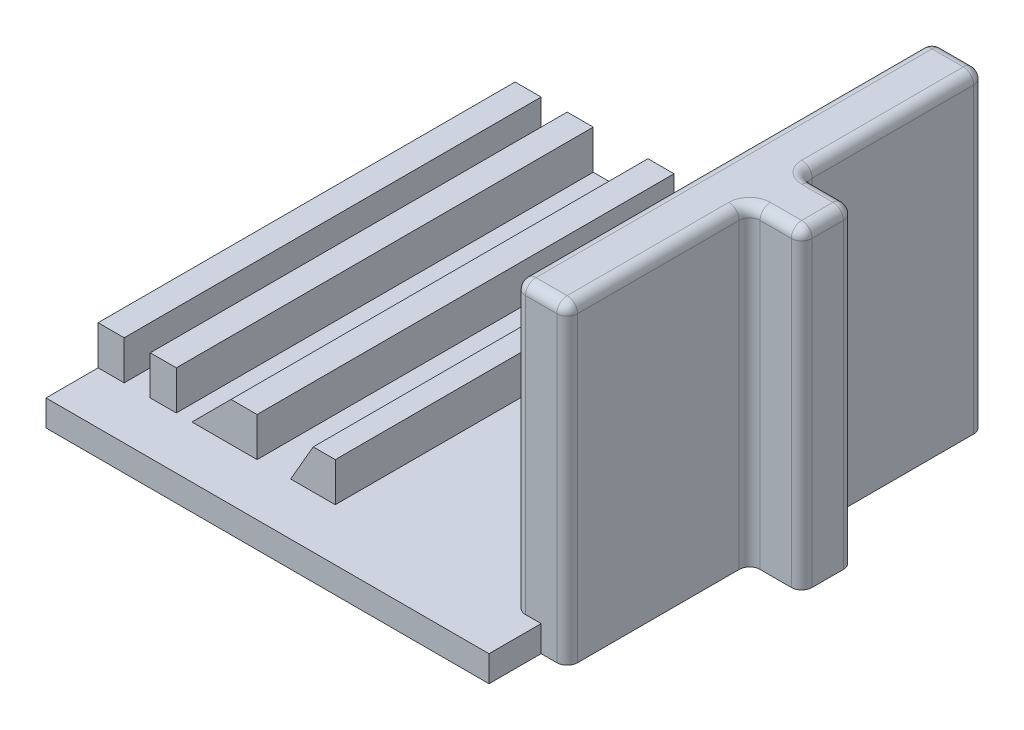
SolidWorks part; units mm, degrees
ref_plane "Front Plane" through (0, 0, 0) normal (0, 0, 1) x (1, 0, 0)
ref_plane "Top Plane" through (0, 0, 0) normal (0, 1, 0) x (1, 0, 0)
ref_plane "Right Plane" through (0, 0, 0) normal (1, 0, 0) x (0, 0, -1)
sketch "Sketch1" plane through (0, 0, 0) normal (0, 1, 0) x (1, 0, 0)
  line L0 (-25.4, 203.2) -> (-25.4, 0)
  line L1 (0, 0) -> (-25.4, 0)
  line L2 (0, 0) -> (0, 203.2)
  line L3 (0, 203.2) -> (-25.4, 203.2)
  line L4 (-25.4, 0) -> (-25.4, 203.2)
  line L5 (-25.4, 203.2) -> (-228.6, 203.2)
  line L6 (-25.4, 0) -> (-228.6, 0)
  line L7 (-228.6, 203.2) -> (-228.6, 0)
  line L8 (0, 101.6) -> (-228.6, 101.6) construction
  line L9 (0, 101.6) -> (104.3179, 101.6)
  line L10 (0, 114.3) -> (0, 88.9)
  line L13 (0, 114.3) -> (25.4, 114.3)
  line L14 (0, 88.9) -> (25.4, 88.9)
  line L15 (25.4, 114.3) -> (25.4, 88.9)
  dimension "D1" = 25.4
  dimension "D2" = 203.2
  dimension "D3" = 88.9
  dimension "D4" = 88.9
  dimension "D5" = 203.2
  dimension "D6" = 25.4
  dimension "D7" = 0
extrude "Boss-Extrude1" add sketch "Sketch1" along normal blind 12.7 contours L8 L0 L5 L7 | L4 L8 L7 L6 region at (-127, 0, -152.4) region at (-127, 0, -50.8)
sketch "Sketch2" plane through (0, 0, 0) normal (0, 1, 0) x (1, 0, 0)
  line L0 (-25.4, 0) -> (-25.4, 203.2)
  line L1 (-25.4, 0) -> (0, 0)
  line L2 (-25.4, 203.2) -> (0, 203.2)
  line L3 (0, 0) -> (0, 203.2)
  dimension "D1" = 25.4
sketch "Sketch3" plane through (0, 0, 0) normal (0, 1, 0) x (1, 0, 0)
  line L0 (0, 88.9) -> (0, 114.3)
  line L1 (0, 88.9) -> (25.4, 88.9)
  line L2 (0, 114.3) -> (25.4, 114.3)
  line L3 (25.4, 88.9) -> (25.4, 114.3)
  line L4 (0, 0) -> (0, 203.2) construction
  line L5 (-25.4, 203.2) -> (-228.6, 203.2) construction
  line L6 (-25.4, 0) -> (-228.6, 0) construction
  dimension "D1" = 88.9
  dimension "D2" = 88.9
  dimension "1" = 25.4
extrude "Boss-Extrude2" add sketch "Sketch2" along normal blind 152.4
extrude "Boss-Extrude3" add sketch "Sketch3" along normal blind 152.4
fillet "Fillet1" radius 5.08 16 edges at (-25.4, 152.4, -101.6) (-12.7, 152.4, -203.2) (0, 152.4, -158.75) (12.7, 152.4, -114.3) (25.4, 152.4, -101.6) (12.7, 152.4, -88.9) (0, 152.4, -44.45) (-12.7, 152.4, 0) (-25.4, 82.55, -203.2) (0, 76.2, -203.2) (0, 76.2, -114.3) (25.4, 76.2, -114.3) (25.4, 76.2, -88.9) (-25.4, 82.55, 0) (0, 76.2, 0) (0, 76.2, -88.9)
sketch "Sketch4" plane through (0, 12.7, 0) normal (0, 1, 0) x (1, 0, 0)
  line L0 (-203.2, 203.2) -> (-203.2, 0)
  line L1 (-203.2, 203.2) -> (-190.5, 203.2)
  line L2 (-203.2, 0) -> (-190.5, 0)
  line L3 (-190.5, 203.2) -> (-190.5, 0)
  line L4 (-20.32, 203.2) -> (-228.6, 203.2) construction
  line L5 (-20.32, 0) -> (-228.6, 0) construction
  line L6 (-228.6, 203.2) -> (-228.6, 0) construction
  line L7 (-189.23, 203.2) -> (-189.23, 0)
  line L8 (-189.23, 203.2) -> (-151.13, 203.2)
  line L9 (-189.23, 0) -> (-151.13, 0)
  line L10 (-151.13, 203.2) -> (-151.13, 0)
  line L11 (-138.43, 203.2) -> (-138.43, 0)
  line L12 (-138.43, 203.2) -> (-113.03, 203.2)
  line L13 (-138.43, 0) -> (-113.03, 0)
  line L14 (-113.03, 203.2) -> (-113.03, 0)
  line L15 (-228.6, 203.2) -> (-228.6, 0)
  line L16 (-228.6, 203.2) -> (-215.9, 203.2)
  line L17 (-228.6, 0) -> (-215.9, 0)
  line L18 (-215.9, 203.2) -> (-215.9, 0)
  dimension "D1" = 25.4
  dimension "D2" = 12.7
  dimension "D3" = 1.27
  dimension "D4" = 38.1
  dimension "D5" = 12.7
  dimension "D6" = 25.4
  dimension "D7" = 12.7
extrude "Boss-Extrude4" add sketch "Sketch4" along normal blind 19.05
chamfer "Chamfer1" distance 25.4 angle 45 1 edges at (-189.23, 31.75, -101.6)
chamfer "Chamfer2" distance 25.4 angle 30 1 edges at (-138.43, 31.75, -101.6) first distance on face at (-138.43, 22.225, -101.6)
sketch "Sketch6" plane through (0, 0, 0) normal (0, 1, 0) x (1, 0, 0)
  line L0 (-228.6, 0) -> (-12.7, 0)
  line L1 (-228.6, 0) -> (-228.6, -25.4)
  line L2 (-12.7, 0) -> (-12.7, -25.4)
  line L3 (-228.6, -25.4) -> (-12.7, -25.4)
  line L4 (-20.32, 0) -> (-113.03, 0) construction
  dimension "D1" = 25.4
  dimension "D2" = 215.9
sketch "Sketch7" plane through (0, 0, 0) normal (0, 0, 1) x (1, 0, 0)
  line L0 (-134.7638, 12.7) -> (-123.7653, 31.75)
  line L1 (-123.7653, 31.75) -> (-4.0299, 239.1378)
  line L2 (-182.88, 12.7) -> (-163.83, 31.75)
  line L3 (-163.83, 31.75) -> (-4.0299, 191.5501)
extrude "Boss-Extrude6" add sketch "Sketch6" along normal blind 12.7
